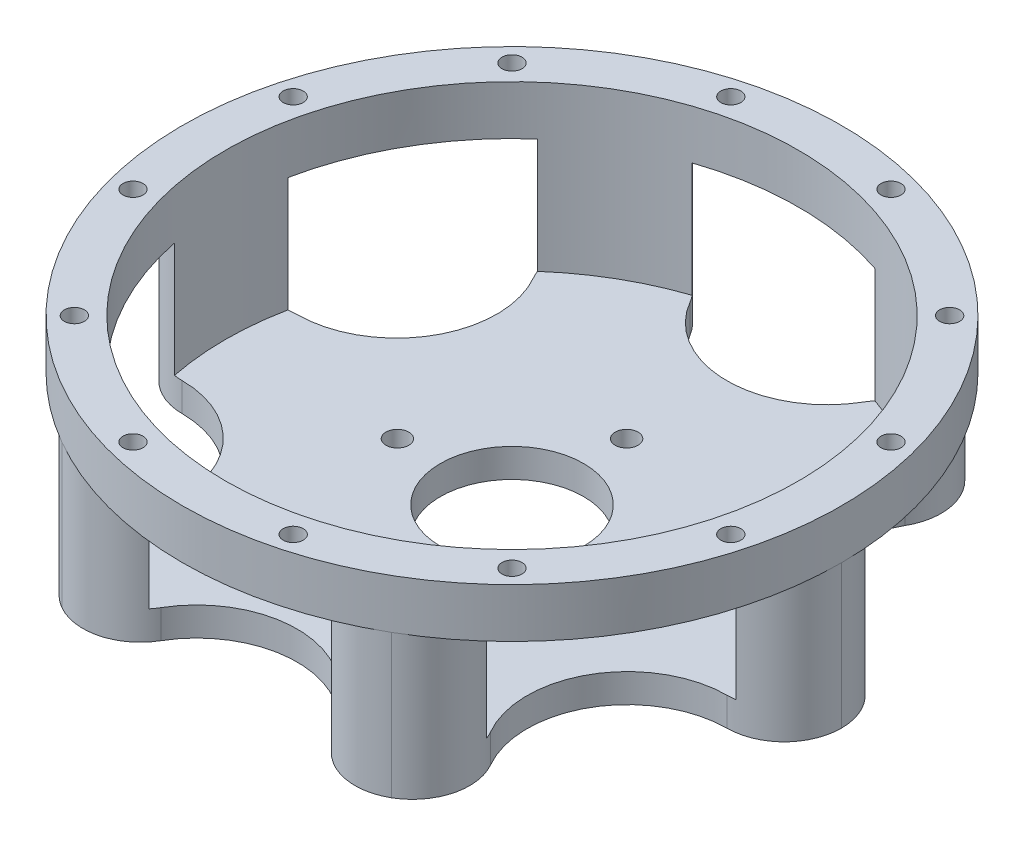
SolidWorks part; units mm, degrees
ref_plane "Front Plane" through (0, 0, 0) normal (0, 0, 1) x (1, 0, 0)
ref_plane "Top Plane" through (0, 0, 0) normal (0, 1, 0) x (1, 0, 0)
ref_plane "Right Plane" through (0, 0, 0) normal (1, 0, 0) x (0, 0, -1)
sketch "Sketch1" plane through (0, 0, 0) normal (0, 1, 0) x (1, 0, 0)
  circle A0 centre (0, 0) radius 57.5
  circle A1 centre (0, 0) radius 55 construction
  point P31 (0, 0)
  dimension "D1" = 115
  dimension "D2" = 110
extrude "Boss-Extrude1" add sketch "Sketch1" along normal blind 33.6
sketch "Sketch2" plane through (0, 33.6, 0) normal (0, 1, 0) x (1, 0, 0)
  circle A0 centre (0, 0) radius 50
  dimension "D1" = 100
extrude "Cut-Extrude1" cut sketch "Sketch2" against normal blind 28.6
sketch "Sketch7" plane through (0, 33.6, 0) normal (0, 1, 0) x (1, 0, 0)
  line L0 (-13.9762, 52.16) -> (0, 0) construction
  line L1 (0, 0) -> (13.9762, 52.16) construction
  line L2 (0, 62.0883) -> (0, -59.7095) construction
  circle A0 centre (0, 0) radius 54 construction
  circle A1 centre (-13.9762, 52.16) radius 1.75
  circle A2 centre (13.9762, 52.16) radius 1.75
  dimension "D1" = 108
  dimension "D4" = 3.5
  dimension "D2" = 15
  dimension "D3" = 15
extrude "Cut-Extrude4" cut sketch "Sketch7" against normal blind 10
sketch "Sketch3" plane through (0, 0, 0) normal (0, -1, 0) x (1, 0, 0)
  line L0 (0, 67.0594) -> (0, -18.0784) construction
  circle A0 centre (0, 0) radius 55 construction
  circle A1 centre (0, 55) radius 17.5
  point P9 (0, 0)
  dimension "D1" = 35
  dimension "D2" = 110
extrude "Cut-Extrude2" cut sketch "Sketch3" against normal blind 25
fillet "Fillet1" radius 10 2 edges at (-17.4985, 12.5, 54.7727) (17.4985, 12.5, 54.7727)
pattern_circular "CirPattern2" count 6 over 360 about axis through (0, 5, 0) along (0, 1, 0) of "Cut-Extrude2", "Fillet1" reverse direction yes
sketch "Sketch5" plane through (0, 0, 0) normal (0, -1, 0) x (1, 0, 0)
  circle A0 centre (0, 0) radius 20 construction
  circle A1 centre (0, 20) radius 2
  circle A2 centre (20, 0) radius 2
  circle A3 centre (0, -20) radius 2
  circle A4 centre (-20, 0) radius 2
  circle A5 centre (0, 0) radius 12.5
  point P14 (0, 0)
  dimension "D1" = 40
  dimension "D2" = 4
  dimension "D4" = 25
  dimension "D3" = 4
extrude "Cut-Extrude3" cut sketch "Sketch5" against normal blind 25
pattern_circular "CirPattern3" count 6 over 360 about axis through (0, 25, 0) along (0, -1, 0) of "Cut-Extrude4" reverse direction yes
